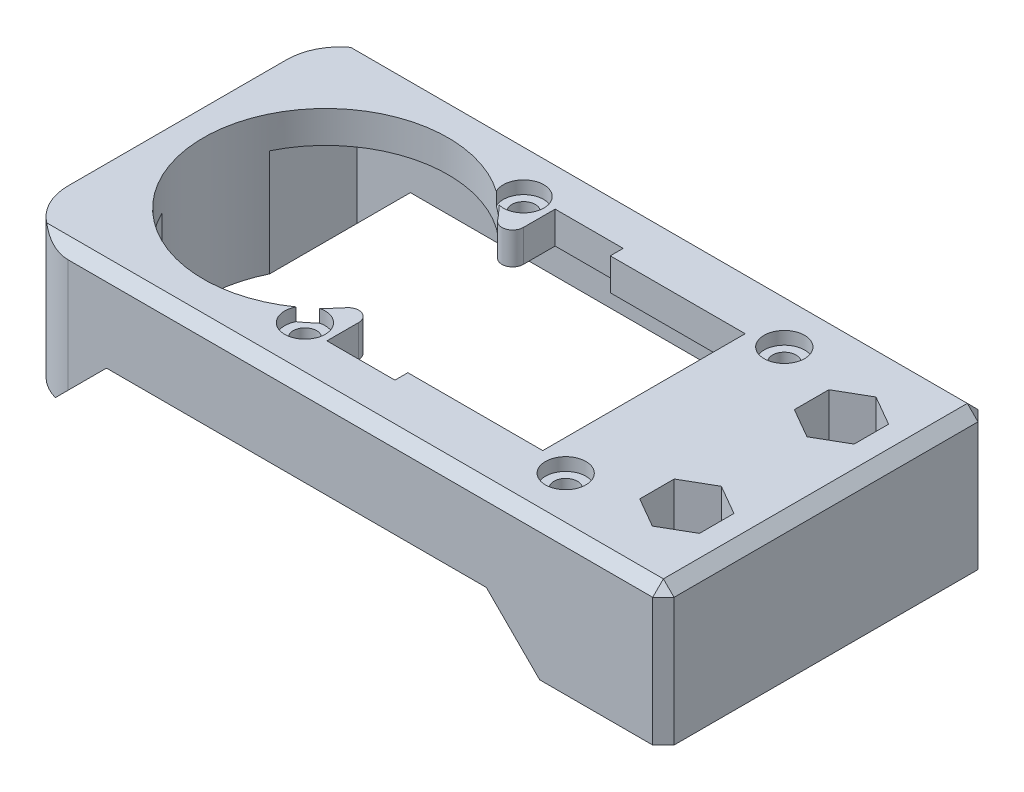
SolidWorks part; units mm, degrees
ref_plane "Plan de face" through (0, 0, 0) normal (0, 0, 1) x (1, 0, 0)
ref_plane "Plan de dessus" through (0, 0, 0) normal (0, 1, 0) x (1, 0, 0)
ref_plane "Plan de droite" through (0, 0, 0) normal (1, 0, 0) x (0, 0, -1)
sketch "Esquisse1" plane through (0, 0, 0) normal (0, 1, 0) x (1, 0, 0)
  line L0 (0, 0) -> (0, 20.5) construction
  line L1 (0, 20.5) -> (24.45, 20.5) construction
  line L2 (24.45, 20.5) -> (24.45, 0) construction
  line L3 (24.45, 0) -> (0, 0) construction
  line L8 (8.89, 19.74) -> (21.54, 19.74)
  line L9 (21.54, 19.74) -> (21.54, 0.76)
  line L10 (21.54, 0.76) -> (8.89, 0.76)
  line L12 (2.51, 20.95) -> (8.89, 20.95)
  line L13 (2.51, 20.95) -> (2.51, -0.45)
  line L14 (2.51, -0.45) -> (8.89, -0.45)
  line L15 (8.89, 20.95) -> (8.89, -0.45)
  line L22 (-21.05, 23.5) -> (-21.05, -3)
  line L24 (29.45, -3) -> (29.45, 23.5)
  line L25 (29.45, 23.5) -> (-21.05, 23.5)
  line L26 (-21.05, -3) -> (29.45, -3)
  circle A0 centre (0, 0) radius 1.1
  circle A1 centre (24.45, 0) radius 1.1
  circle A2 centre (24.45, 20.5) radius 1.1
  circle A3 centre (0, 20.5) radius 1.1
  circle A8 centre (-8.3, 10.25) radius 11.48
  point P17 (21.54, 10.25)
  point P22 (24.45, 10.25)
  point P28 (8.89, 10.25)
  point P31 (0, 10.25)
  dimension "D1" = 2.2
  dimension "D4" = 12.75
  dimension "D14" = 22.96
  dimension "D2" = 20.5
  dimension "D3" = 24.45
  dimension "D9" = 18.98
  dimension "D10" = 12.65
  dimension "D11" = 6.38
  dimension "D12" = 21.4
  dimension "D13" = 2.91
  dimension "D15" = 8.3
  dimension "D22" = 3
  dimension "D23" = 5
  dimension "D24" = 3
extrude "Boss.-Extru.1" add sketch "Esquisse1" along normal blind 3 contours L24 L25 L22 A8 L13 L12 L15 L8 L9 L10 L14 A3 A2 A1 A0 region at (4.2, 0, -22.9297)
fillet "Congé1" radius 1 2 edges at (2.51, 1.5, -14.1145) (2.51, 1.5, -6.3855)
hole_wizard "Chambrage pour vis à six pans creux M1.61" positions "Esquisse2" profile "Esquisse3" counterbore size "M1.6" standard "ISO" end condition through all
sketch "Esquisse2" plane through (0, 3, 0) normal (0, 1, 0) x (1, 0, 0)
  point P12 (0, 0)
  point P15 (0, 20.5)
  point P18 (24.45, 20.5)
  point P21 (24.45, 0)
sketch "Esquisse3" plane through (0, 3, 0) normal (1, 0, 0) x (0, 0, 1)
  line L0 (0, 0) -> (0, 3)
  line L1 (0, 3) -> (1.1, 3)
  line L3 (1.1, 3) -> (1.1, 1.2)
  line L4 (1.1, 1.2) -> (1.9, 1.2)
  line L5 (1.9, 1.2) -> (1.9, 0)
  line L7 (1.9, 0) -> (0, 0)
  line L11 (0, -6.35) -> (0, 107.95) construction
  dimension "Diamètre du perçage jusqu'au prochain" = 2.2
  dimension "Profondeur du perçage jusqu'au prochain" = 3
  dimension "Diamètre du chambrage" = 3.8
  dimension "Profondeur du chambrage" = 1.2
sketch "Esquisse4" plane through (0, 3, 0) normal (0, 1, 0) x (1, 0, 0)
  line L0 (-21.05, 23.5) -> (-21.05, -3) construction
  line L1 (-18.61, 23.5) -> (-30.21, 23.5)
  line L2 (-18.61, 23.5) -> (-18.61, 15.2992)
  line L3 (-18.61, -3) -> (-30.21, -3)
  line L4 (-30.21, 23.5) -> (-30.21, -3)
  line L5 (29.45, 23.5) -> (-21.05, 23.5) construction
  line L6 (27.01, 23.5) -> (38.61, 23.5)
  line L12 (-18.61, 15.2992) -> (-18.61, 5.2008) construction
  line L13 (-18.61, 5.2008) -> (-18.61, -3)
  line L14 (27.01, 23.5) -> (27.01, -3)
  line L16 (-30.21, 17.5) -> (-18.61, 17.5) construction
  line L17 (-30.21, 10.25) -> (-56.6243, 10.25) construction
  line L18 (4.2, 23.5) -> (4.2, 41.2903) construction
  line L19 (-21.05, -3) -> (29.45, -3) construction
  line L20 (27.01, -3) -> (38.61, -3)
  line L21 (38.61, -3) -> (38.61, 23.5)
  line L22 (29.45, -3) -> (29.45, 23.5) construction
  arc A0 (-1.6935, 19.6385) -> (-1.6935, 0.8615) centre (-8.3, 10.25) ccw construction
  arc A1 (-18.61, 15.2992) -> (-18.61, 5.2008) centre (-8.3, 10.25) ccw
  circle A2 centre (-24.41, 10.25) radius 1.6
  circle A5 centre (32.81, 3) radius 1.6
  arc A6 (-18.61, 5.2008) -> (-1.6935, 0.8615) centre (-8.3, 10.25) ccw construction
  arc A7 (-1.6935, 19.6385) -> (-18.61, 15.2992) centre (-8.3, 10.25) ccw construction
  circle A10 centre (32.81, 17.5) radius 1.6
  dimension "D5" = 6
  dimension "D8" = 3.2
  dimension "D1" = 9.16
  dimension "D2" = 11.6
  dimension "D3" = 9.16
  dimension "D4" = 11.6
  dimension "D6" = 6
  dimension "D7" = 5.8
  dimension "D9" = 6
  dimension "D10" = 5.8
extrude "Boss.-Extru.2" add sketch "Esquisse4" against normal blind 19
sketch "Esquisse5" plane through (0, -16, 0) normal (0, -1, 0) x (1, 0, 0)
  line L1 (-24.41, -7.0168) -> (-27.21, -8.6334)
  line L2 (-27.21, -8.6334) -> (-27.21, -11.8666)
  line L3 (-27.21, -11.8666) -> (-24.41, -13.4832)
  line L4 (-24.41, -13.4832) -> (-21.61, -11.8666)
  line L5 (-21.61, -11.8666) -> (-21.61, -8.6334)
  line L6 (-21.61, -8.6334) -> (-24.41, -7.0168)
  line L13 (32.81, -14.2668) -> (30.01, -15.8834)
  line L14 (30.01, -15.8834) -> (30.01, -19.1166)
  line L15 (30.01, -19.1166) -> (32.81, -20.7332)
  line L16 (32.81, -20.7332) -> (35.61, -19.1166)
  line L17 (35.61, -19.1166) -> (35.61, -15.8834)
  line L18 (35.61, -15.8834) -> (32.81, -14.2668)
  line L19 (32.81, 0.2332) -> (30.01, -1.3834)
  line L20 (30.01, -1.3834) -> (30.01, -4.6166)
  line L21 (30.01, -4.6166) -> (32.81, -6.2332)
  line L22 (32.81, -6.2332) -> (35.61, -4.6166)
  line L23 (35.61, -4.6166) -> (35.61, -1.3834)
  line L24 (35.61, -1.3834) -> (32.81, 0.2332)
  circle A0 centre (-24.41, -10.25) radius 2.8 construction
  circle A2 centre (32.81, -17.5) radius 2.8 construction
  circle A3 centre (32.81, -3) radius 2.8 construction
  dimension "D1" = 5.6
extrude "Enlèv. mat.-Extru.1" cut sketch "Esquisse5" along normal blind 7 from surface starting at face at (4.2, 3, -10.25)
sketch "Esquisse6" plane through (0, 0, -23.5) normal (0, 0, -1) x (-1, 0, 0)
  line L0 (-38.61, -16) -> (-38.61, 3) construction
  line L1 (-27.01, -16) -> (-38.61, -16)
  line L2 (-27.01, -16) -> (-27.01, -10)
  line L3 (-27.01, -10) -> (-38.61, -10)
  line L4 (-38.61, -16) -> (-38.61, -10)
  line L5 (-27.01, 0) -> (18.61, 0) construction
  line L6 (30.21, -16) -> (30.21, 3) construction
  line L7 (18.61, -16) -> (30.21, -16)
  line L8 (18.61, -16) -> (18.61, -10)
  line L9 (18.61, -10) -> (30.21, -10)
  line L10 (30.21, -16) -> (30.21, -10)
  dimension "D1" = 10
  dimension "D2" = 10
extrude "Enlèv. mat.-Extru.2" cut sketch "Esquisse6" against normal through all
ref_plane "Plan1" through (0, 0, -10.25) normal (0, 0, -1) x (-1, 0, 0)
sketch "Esquisse7" plane through (0, 0, -23.5) normal (0, 0, -1) x (-1, 0, 0)
  line L0 (-4.2, 0) -> (-4.2, 16.2892) construction
  line L3 (-27.01, -10) -> (-17.01, 0)
  line L4 (18.61, -10) -> (8.61, 0)
  line L5 (-22.01, -5) -> (13.61, -5)
  line L12 (-38.61, -10) -> (-27.01, -10)
  line L14 (-27.01, -10) -> (-27.01, 0)
  line L25 (-27.01, 0) -> (18.61, 0)
  line L26 (18.61, 0) -> (18.61, -10)
  line L28 (18.61, -10) -> (30.21, -10)
  line L29 (30.21, -10) -> (30.21, 3)
  line L30 (30.21, 3) -> (-38.61, 3)
  line L31 (-38.61, 3) -> (-38.61, -10)
  line L32 (-38.61, -10) -> (-27.01, -10)
  line L34 (-17.01, 0) -> (8.61, 0)
  line L36 (18.61, -10) -> (30.21, -10)
  line L37 (30.21, -10) -> (30.21, 3)
  line L38 (30.21, 3) -> (-38.61, 3)
  line L39 (-38.61, 3) -> (-38.61, -10)
  line M12 (-38.61, -10) -> (-27.01, -10)
  line M13 (-27.01, -10) -> (-27.01, 0)
  line M14 (-27.01, 0) -> (18.61, 0)
  line M15 (18.61, 0) -> (18.61, -10)
  line M17 (30.21, -10) -> (30.21, 3)
  line M18 (30.21, 3) -> (-38.61, 3)
  line M19 (-38.61, 3) -> (-38.61, -10)
  line M20 (18.61, -10) -> (30.21, -10)
  dimension "D2" = 10
  dimension "D1" = 0
extrude "Boss.-Extru.3" add sketch "Esquisse7" along normal blind 2 contours L3 L5 L4 L34 M14 | L3 M13 M14 | L0 L38 M14 M19 M12 M13 | L4 M15 M14 | L0 L34 M14 M15 M20 M17 M18 region at (27.4397, -1.9393, -23.5) region at (4.2, -2.6361, -23.5) region at (-19.0397, -1.9393, -23.5) region at (23.6767, -3.3333, -23.5) region at (-15.2767, -3.3333, -23.5)
mirror "Symétrie1" about plane through (0, 0, -10.25) normal (0, 0, -1) of "Boss.-Extru.3"
sketch "Esquisse10" plane through (0, 3, 0) normal (0, 1, 0) x (1, 0, 0)
  circle A0 centre (-24.41, 10.25) radius 4
  dimension "D1" = 8
extrude "Boss.-Extru.5" add sketch "Esquisse10" against normal up to surface (13 mm away) up to face at (-21.6562, -10, -10.25)
sketch "Esquisse11" plane through (0, 3, 0) normal (0, 1, 0) x (1, 0, 0)
  line L0 (-22.21, 25.5) -> (-22.21, -5)
  line L4 (38.61, -5) -> (38.61, 25.5)
  line L5 (38.61, 25.5) -> (-30.21, 25.5)
  line L6 (-30.21, 25.5) -> (-30.21, -5)
  line L7 (-30.21, -5) -> (38.61, -5)
  line L9 (-22.21, 25.5) -> (-30.21, 25.5)
  line L10 (-30.21, 25.5) -> (-30.21, -5)
  line L11 (-30.21, -5) -> (-22.21, -5)
  dimension "D2" = 8
  dimension "D1" = 0
extrude "Enlèv. mat.-Extru.5" cut sketch "Esquisse11" against normal through all
chamfer "Chanfrein1" distance 1 angle 45 5 edges at (38.61, 3, -10.25) (38.61, -3.5, 5) (38.61, -3.5, -25.5) (8.2, 3, 5) (8.2, 3, -25.5)
fillet "Congé2" radius 5 2 edges at (-22.21, -4, -25.5) (-22.21, -4, 5)
